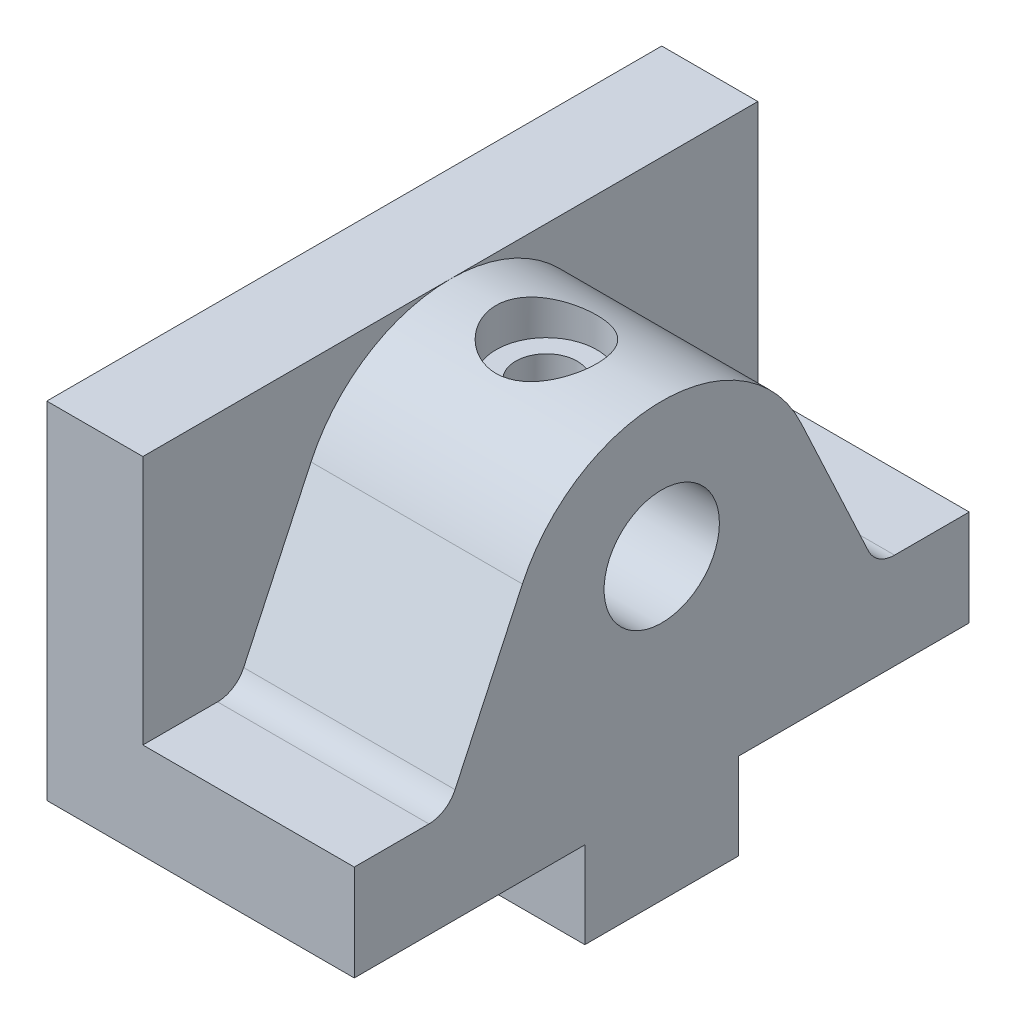
SolidWorks part; units mm, degrees
ref_plane "Front Plane" through (0, 0, 0) normal (0, 0, 1) x (1, 0, 0)
ref_plane "Top Plane" through (0, 0, 0) normal (0, 1, 0) x (1, 0, 0)
ref_plane "Right Plane" through (0, 0, 0) normal (1, 0, 0) x (0, 0, -1)
sketch "Sketch2" plane through (0, 0, 0) normal (1, 0, 0) x (0, 0, -1)
  line L0 (-8, 0) -> (8, 0)
  line L1 (8, 0) -> (8, 9)
  line L2 (-8, 0) -> (-8, 9)
  line L3 (-8, 9) -> (-32, 9)
  line L4 (8, 9) -> (32, 9)
  line L5 (-32, 9) -> (-32, 19)
  line L6 (32, 9) -> (32, 19)
  line L7 (-21.5094, 20.7321) -> (-14.5009, 35.7619)
  line L8 (-32, 19) -> (-24.2283, 19)
  line L9 (14.5009, 35.7619) -> (21.5094, 20.7321)
  line L10 (32, 19) -> (24.2283, 19)
  line L11 (-32, 19) -> (-32, 45)
  line L12 (-32, 45) -> (32, 45)
  line L13 (32, 19) -> (32, 45)
  line L14 (0, 0) -> (0, 31) construction
  line L15 (0, 45) -> (0, 37) construction
  arc A0 (-14.5009, 35.7619) -> (14.5009, 35.7619) centre (0, 29) cw
  arc A1 (21.5094, 20.7321) -> (24.2283, 19) centre (24.2283, 22) ccw
  arc A2 (-21.5094, 20.7321) -> (-24.2283, 19) centre (-24.2283, 22) cw
  circle A3 centre (0, 31) radius 6
  point P4 (0, 0)
  point P22 (0, 45)
  point P26 (22.3171, 19)
  point P29 (-22.3171, 19)
  dimension "D5" = 16
  dimension "D8" = 3
  dimension "D10" = 12
  dimension "D1" = 16
  dimension "D2" = 64
  dimension "D3" = 9
  dimension "D4" = 50
  dimension "D6" = 10
  dimension "D7" = 36
  dimension "D9" = 31
  dimension "D11" = 8
extrude "Boss-Extrude1" add sketch "Sketch2" along normal blind 32 contours L7 A2 L8 L5 L3 L2 L0 L1 L4 L6 L10 A1 L9 A0 region at (0, 20.4295, 0)
extrude "Boss-Extrude2" add sketch "Sketch2<5>" along normal blind 10 contours A2 L7 A0 L12 L11 L8 | L9 A1 L10 L13 L12 A0 region at (0, 34.0824, 23.1205) region at (0, 34.0824, -23.1205)
sketch "Sketch2<5>" plane through (0, 0, 0) normal (1, 0, 0) x (0, 0, -1) same geometry as "Sketch2"
sketch "Sketch3" plane through (0, 45, 0) normal (0, 1, 0) x (1, 0, 0)
  line L0 (0, 0) -> (8, 0) construction
  line L1 (8, 0) -> (20, 0) construction
  line L2 (20, 0) -> (24, 0) construction
hole_wizard "CBORE for M6 SHCS1" positions "3DSketch1" profile "Sketch4" counterbore size "M6" standard "ANSI Metric"
sketch3d "3DSketch1"
  point P0 (20, 45, 0)
sketch "Sketch4" plane through (20, 45, 0) normal (1, 0, 0) x (0, 0, 1)
  line L0 (0, 0) -> (0, 11.9228)
  line L1 (0, 11.9228) -> (3.2, 10)
  line L2 (3.2, 10) -> (3.2, 4)
  line L3 (3.2, 4) -> (5.25, 4)
  line L4 (5.25, 4) -> (5.25, 0)
  line L5 (5.25, 0) -> (0, 0)
  line L10 (0, 11.9228) -> (-3.2, 10) construction
  line L11 (0, -6.35) -> (0, 107.95) construction
  dimension "Hole Dia." = 6.4
  dimension "Hole Depth" = 10
  dimension "C'Bore Dia." = 10.5
  dimension "C'Bore Depth" = 4
  dimension "Drill Angle" = 118
hole_wizard "Tap Drill for M6x1.0 Tap1" positions "Sketch5" profile "Sketch6" hole size "M6x1.0" standard "ANSI Metric"
sketch "Sketch5" plane through (0, 0, 0) normal (0, -1, 0) x (-1, 0, 0)
  point P0 (-24, 0)
  point P3 (-8, 0)
sketch "Sketch6" plane through (24, 0, 0) normal (1, 0, 0) x (0, 0, -1)
  line L0 (0, 0) -> (0, 17.5022)
  line L1 (0, 17.5022) -> (2.5, 16)
  line L2 (2.5, 16) -> (2.5, 0)
  line L5 (2.5, 0) -> (0, 0)
  line L10 (0, 17.5022) -> (-2.5, 16) construction
  line L11 (0, -6.35) -> (0, 107.95) construction
  dimension "Hole Dia." = 5
  dimension "Hole Depth" = 16
  dimension "Drill Angle" = 118
extrude "Boss-Extrude3" add sketch "Sketch2<6>" along normal blind 10 contours A3 region at (0, 31, 0)
sketch "Sketch2<6>" plane through (0, 0, 0) normal (1, 0, 0) x (0, 0, -1) same geometry as "Sketch2"
